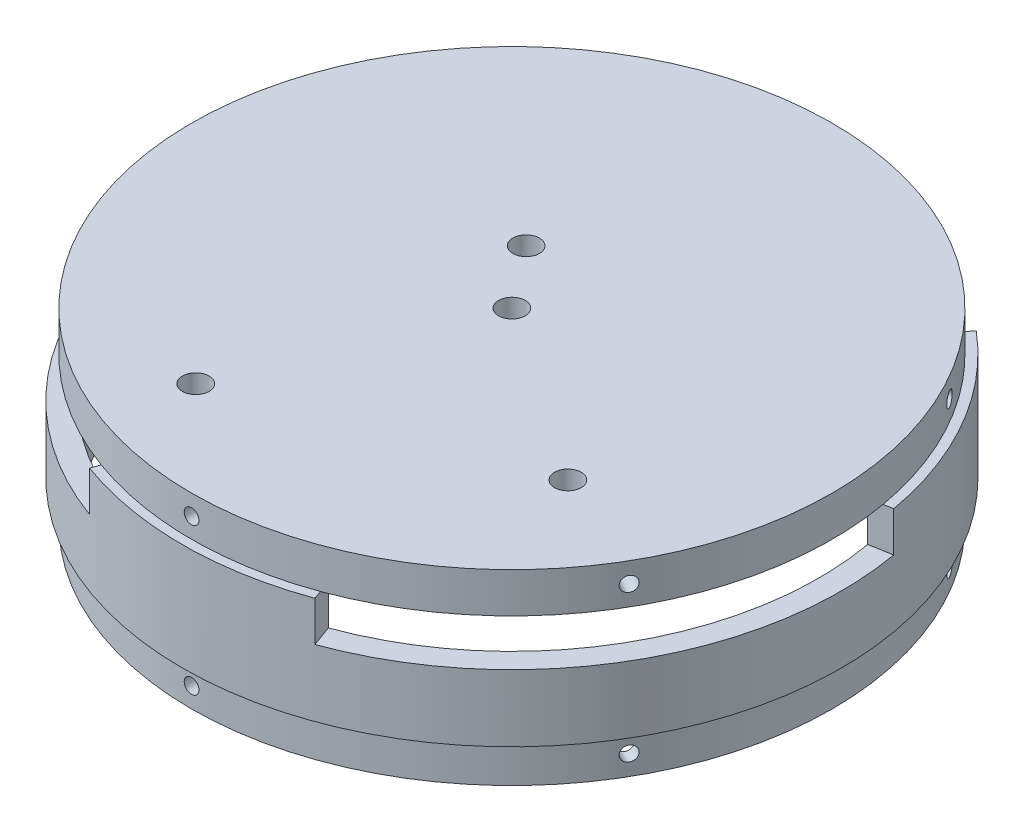
SolidWorks part; units mm, degrees
ref_plane "Front Plane" through (0, 0, 0) normal (0, 0, 1) x (1, 0, 0)
ref_plane "Top Plane" through (0, 0, 0) normal (0, 1, 0) x (1, 0, 0)
ref_plane "Right Plane" through (0, 0, 0) normal (1, 0, 0) x (0, 0, -1)
sketch "Sketch1" plane through (0, 0, 0) normal (0, 1, 0) x (1, 0, 0)
  line L0 (0, 0) -> (-50.3682, 60.0265)
  line L1 (0, 0) -> (50.3682, 60.0265)
  line L2 (0, 0) -> (0, 72.1431) construction
  circle A0 centre (0, 0) radius 78.359
  circle A1 centre (0, 0) radius 73.025
  circle A2 centre (0, 0) radius 76.1746
  dimension "D1" = 156.718
  dimension "D2" = 146.05
  dimension "D3" = 152.3492
  dimension "D4" = 80
extrude "Boss-Extrude1" add sketch "Sketch1" along normal blind 25.4 contours L2 A2 L1 A0 | L2 A1 L1 A2 | L2 A2 L1 A1 | L2 A0 L1 A2 | A2 L2 A1 L0 | A0 L2 A2 L0 | A2 L2 A0 L0 | A1 L2 A2 L0 region at (-31.7206, 0, 68.0251) region at (-47.1858, 0, -57.7895) region at (-33.0764, 0, 70.9325) region at (-48.8794, 0, -59.85)
ref_plane "Plane1" through (0, 12.7, 0) normal (0, 1, 0) x (1, 0, 0)
extrude "Boss-Extrude2" add sketch "Sketch1<3>" along normal blind 9.525 from surface contours A2 L2 A1 L0 | L2 A2 L1 A1 | L2 A1 L1 A2 | A1 L2 A2 L0 region at (-31.7206, 0, 68.0251) region at (-47.1858, 0, -57.7895) starting at face at (0, 25.4, 73.025)
sketch "Sketch1<3>" plane through (0, 0, 0) normal (0, 1, 0) x (1, 0, 0) same geometry as "Sketch1"
extrude "Boss-Extrude3" add sketch "Sketch1<4>" against normal blind 9.525 contours A2 L2 A1 L0 | A1 L2 A2 L0 | L2 A1 L1 A2 | L2 A2 L1 A1 region at (-31.7206, 0, 68.0251) region at (-47.1858, 0, -57.7895)
sketch "Sketch1<4>" plane through (0, 0, 0) normal (0, 1, 0) x (1, 0, 0) same geometry as "Sketch1"
ref_plane "Plane2" through (0, 0, -76.1746) normal (0, 0, -1) x (-1, 0, 0)
ref_plane "Plane5" through (0, 25.4, 0) normal (0, 1, 0) x (1, 0, 0)
ref_axis "Axis1" through (0, 0, 0) along (0, 1, 0)
sketch "Sketch3" plane through (0, 0, -76.1746) normal (0, 0, -1) x (-1, 0, 0)
  line L0 (76.1746, 0) -> (-76.1746, 0) construction
  line L1 (-76.1746, -9.525) -> (76.1746, -9.525) construction
  line L2 (76.1746, 25.4) -> (-76.1746, 25.4) construction
  line L3 (76.1746, 34.925) -> (-76.1746, 34.925) construction
  line L4 (76.1746, 0) -> (-76.1746, 0)
  line L5 (-76.1746, -9.525) -> (76.1746, -9.525)
  line L6 (76.1746, 25.4) -> (-76.1746, 25.4)
  line L7 (76.1746, 34.925) -> (-76.1746, 34.925)
  line L8 (0, 34.925) -> (0, 25.4)
  line L9 (0, 0) -> (0, -9.525)
  circle A0 centre (0, 30.1625) radius 1.75
  circle A1 centre (0, -4.7625) radius 1.75
  point P12 (0, 30.1625)
  point P13 (0, -4.7625)
  point P14 (-77.5445, 179.1871)
  dimension "D1" = 3.5
extrude "Cut-Extrude2" cut sketch "Sketch3" against normal blind 9.525 contours L8 A0 | L8 A0 | L9 A1 | L9 A1 region at (-0.7427, 30.1625, -76.1746) region at (0.7427, 30.1625, -76.1746) region at (-0.7427, -4.7625, -76.1746) region at (0.7427, -4.7625, -76.1746)
extrude "Cut-Extrude3" cut sketch "Sketch1<7>" against normal blind 9.525 from surface contours L2 A1 L1 A2 | A1 L2 A2 L0 | A2 L2 A0 L0 | L2 A2 L1 A0 region at (-47.1858, 0, -57.7895) region at (-48.8794, 0, -59.85) starting at plane "Plane5"
sketch "Sketch1<7>" plane through (0, 0, 0) normal (0, 1, 0) x (1, 0, 0) same geometry as "Sketch1"
pattern_circular "CirPattern2" count 3 over 360 about axis through (0, 0, 0) along (0, 1, 0) of "Cut-Extrude3"
ref_plane "Plane3" through (0, 34.925, 0) normal (0, 1, 0) x (1, 0, 0)
sketch "Sketch4" plane through (0, 34.925, 0) normal (0, 1, 0) x (1, 0, 0)
  circle A0 centre (0, 0) radius 73.025
  dimension "D1" = 146.05
extrude "Boss-Extrude4" add sketch "Sketch4" against normal blind 9.525
pattern_circular "CirPattern3" count 6 over 360 about axis through (0, 0, 0) along (0, 1, 0) of "Cut-Extrude2"
sketch "Sketch5" plane through (0, 34.925, 0) normal (0, 1, 0) x (1, 0, 0)
  line L0 (-15.0069, -36.2322) -> (-26.8004, -73.6334) construction
  line L1 (-15.0069, -36.2322) -> (-22.0157, -53.1519) construction
  circle A0 centre (0, 0) radius 3.175
  circle A1 centre (-22.0157, -53.1519) radius 3.175
  circle A2 centre (0, 0) radius 57.531 construction
  circle A3 centre (23.8745, -31.1125) radius 57.531 construction
  circle A4 centre (-11.1485, 14.5297) radius 3.175
  circle A5 centre (-15.0069, -36.2322) radius 57.531 construction
  circle A6 centre (42.0318, -28.7224) radius 3.175
  point P17 (2.9559, -22.4482)
  dimension "D1" = 6.35
  dimension "D3" = 6.35
  dimension "D2" = 57.531
  dimension "D5" = 5
extrude "Cut-Extrude4" cut sketch "Sketch5" against normal through all
equation "\"AB_Coupler_OD_Length\"= 1in"
equation "\"AB_Coupling_Section_Length\"= 0.375in"
equation "\"AB_Coupler_Length\"= \"AB_Coupler_OD_Length\" + \"AB_Coupling_Section_Length\" * 2"
equation "\"D1@Boss-Extrude2\"=\"AB_Coupling_Section_Length\""
equation "\"D1@Boss-Extrude3\"=\"AB_Coupling_Section_Length\""
equation "\"D1@Boss-Extrude1\" = \"AB_Coupler_OD_Length\""
equation "\"Cutout_Angle\" = 80"
equation "\"AB_Coupler_Num_Screws\"= 6"
equation "\"Num_Cutouts\" = 3"
equation "\"D4@Sketch1\"=\"Cutout_Angle\""
equation "\"D1@CirPattern2\"=\"Num_Cutouts\""
equation "\"D1@CirPattern3\"=\"AB_Coupler_Num_Screws\""
equation "\"AB_Coupler_OD\"= 6.17in"
equation "\"AB_Coupler_ID\"= 5.75in"
equation "\"AB_Coupler_Surface_Diameter\"= 5.998in"
equation "\"D3@Sketch1\"=\"AB_Coupler_Surface_Diameter\""
equation "\"D2@Sketch1\"=\"AB_Coupler_ID\""
equation "\"D1@Sketch1\"=\"AB_Coupler_OD\""
equation "\"AB_Coupling_Screw_Diameter\"= 0.1065in"
equation "\"Aft_Section_Length\"= 40in"
equation "\"Aft_Lower_Length\"= 20in"
equation "\"Aft_Upper_Length\"= \"Aft_Section_Length\" - \"Aft_Lower_Length\" - \"AB_Coupler_OD_Length\""
equation "\"Mid_Coupler_Length\" = 13in"
equation "\"Lead_Screw_Dist\" = 2.25in"
equation "\"Lead_Screw_Diam\" = (27/64)*1in"
equation "\"Lead_Screw_Length\" = (\"Mid_Coupler_Length\" + 2*0.375in + 2*0.5in)"
equation "\"Bodytube_OD\" = 6.17in"
equation "\"Paddle_Pin_Offset\" = .25in"
equation "\"Bodytube_ID\" = 5.998in"
equation "\"Paddle_Pin_Radius\" = 2.25in"
equation "\"D1@Sketch4\"=\"AB_Coupler_ID\""
equation "\"D2@Sketch5\"=2.265"
